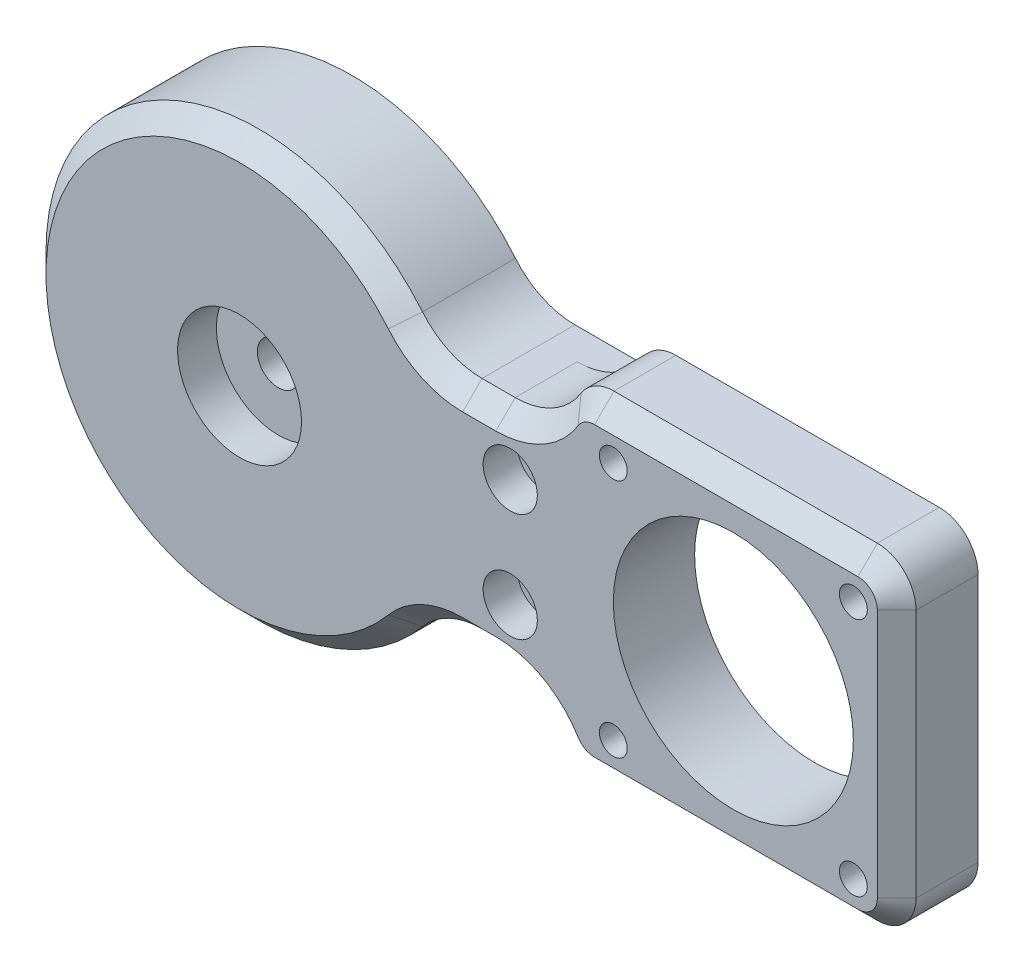
SolidWorks part; units mm, degrees
material "ABS"
ref_plane "Front Plane" through (0, 0, 0) normal (0, 0, 1) x (1, 0, 0)
ref_plane "Top Plane" through (0, 0, 0) normal (0, 1, 0) x (1, 0, 0)
ref_plane "Right Plane" through (0, 0, 0) normal (1, 0, 0) x (0, 0, -1)
sketch "Sketch1" plane through (0, 0, 0) normal (0, 0, 1) x (1, 0, 0)
  line L0 (42.6696, 14) -> (42.6696, 21.1)
  line L1 (23.6696, -14) -> (42.6696, -14)
  line L3 (23.6696, 14) -> (42.6696, 14)
  line L7 (42.6696, -21.1) -> (84.8696, -21.1)
  line L8 (42.6696, -21.1) -> (42.6696, -14)
  line L9 (42.6696, 21.1) -> (84.8696, 21.1)
  line L10 (84.8696, -21.1) -> (84.8696, 21.1)
  line L11 (42.6696, -21.1) -> (84.8696, 21.1) construction
  line L12 (42.6696, 21.1) -> (84.8696, -21.1) construction
  line L13 (48.2696, -15.5) -> (79.2696, -15.5) construction
  line L14 (48.2696, -15.5) -> (48.2696, 15.5) construction
  line L15 (48.2696, 15.5) -> (79.2696, 15.5) construction
  line L16 (79.2696, -15.5) -> (79.2696, 15.5) construction
  line L17 (48.2696, -15.5) -> (79.2696, 15.5) construction
  line L18 (48.2696, 15.5) -> (79.2696, -15.5) construction
  arc A0 (23.6696, 14) -> (23.6696, -14) centre (0, 0) ccw
  circle A2 centre (63.7696, 0) radius 15.5
  circle A3 centre (48.2696, 15.5) radius 1.5
  circle A4 centre (79.2696, 15.5) radius 1.5
  circle A5 centre (79.2696, -15.5) radius 1.5
  circle A6 centre (48.2696, -15.5) radius 1.5
  circle A7 centre (0, 0) radius 2.7
  point P3 (27.5, 0)
  point P8 (63.7696, 0)
  point P18 (63.7696, 0)
  dimension "D7" = 31
  dimension "D8" = 27.5
  dimension "D3" = 5.4
  dimension "D1" = 28
  dimension "D2" = 42.2
  dimension "D4" = 19
  dimension "D5" = 42.2
  dimension "D6" = 31
extrude "Boss-Extrude1" add sketch "Sketch1" along normal blind 14.5
ref_plane "Plane1" through (0, 0, 14.5) normal (0, 0, 1) x (1, 0, 0)
sketch "Sketch2" plane through (0, 0, 0) normal (0, 0, -1) x (-1, 0, 0)
  line L1 (-84.8696, -21.1) -> (-42.6696, -21.1)
  line L2 (-84.8696, -21.1) -> (-84.8696, 21.1)
  line L3 (-84.8696, 21.1) -> (-42.6696, 21.1)
  line L4 (-42.6696, -21.1) -> (-42.6696, 21.1)
  line L5 (-84.8696, -21.1) -> (-42.6696, 21.1) construction
  line L6 (-84.8696, 21.1) -> (-42.6696, -21.1) construction
  circle A0 centre (-63.7696, 0) radius 15.5 construction
  point P0 (-63.7696, 0)
extrude "Cut-Extrude1" cut sketch "Sketch2" against normal blind 4
sketch "Sketch3" plane through (0, 0, 14.5) normal (0, 0, 1) x (1, 0, 0)
  circle A0 centre (0, 0) radius 8
  dimension "D1" = 16
extrude "Cut-Extrude2" cut sketch "Sketch3" against normal blind 5
fillet "Fillet2" radius 10 4 edges at (42.6696, -14, 9.25) (42.6696, 14, 9.25) (23.6696, -14, 7.25) (23.6696, 14, 7.25)
sketch "Sketch5" plane through (0, 0, 14.5) normal (0, 0, 1) x (1, 0, 0)
  point P0 (79.2696, -15.5)
  point P3 (79.2696, 15.5)
  point P6 (48.2696, 15.5)
  point P9 (48.2696, -15.5)
hole_wizard "Taladro de margen para M31" positions "Sketch5" profile "Sketch6" hole size "M3" standard "Ansi Metric" end condition through all
sketch "Sketch6" plane through (79.2696, -15.5, 14.5) normal (1, 0, 0) x (0, -1, 0)
  line L0 (0, 0) -> (0, 14.5)
  line L1 (0, 14.5) -> (1.8, 14.5)
  line L2 (1.8, 14.5) -> (1.8, 0)
  line L5 (1.8, 0) -> (0, 0)
  line L11 (0, -6.35) -> (0, 107.95) construction
  dimension "Diámetro de taladro hasta el siguiente" = 3.6
  dimension "Profundidad de taladro hasta el siguiente" = 14.5
sketch "Sketch7" plane through (0, 0, 14.5) normal (0, 0, 1) x (1, 0, 0)
  line L0 (30.9567, 14) -> (30.9567, -14) construction
  line L1 (33.0993, 14) -> (28.8141, 14) construction
  line L2 (28.8141, -14) -> (33.0993, -14) construction
  line L3 (-969.0433, 0) -> (49030.9567, 0) construction
  line L4 (34.9567, -14) -> (34.9567, 14) construction
  circle A0 centre (34.9567, 7) radius 1.5
  circle A1 centre (34.9567, -7) radius 1.5
  point P11 (30.9567, 0)
  dimension "D2" = 3
  dimension "D1" = 7
  dimension "D3" = 7
  dimension "D4" = 4
extrude "Cut-Extrude3" cut sketch "Sketch7" against normal through all
sketch "Sketch8" plane through (0, 0, 14.5) normal (0, 0, 1) x (1, 0, 0)
  point P0 (34.9567, 7)
  point P3 (34.9567, -7)
hole_wizard "Refrentado para tornillo con cabeza troncocónica de M31" positions "Sketch8" profile "Sketch9" counterbore size "M3" standard "Ansi Metric" end condition through all
sketch "Sketch9" plane through (34.9567, 7, 14.5) normal (1, 0, 0) x (0, -1, 0)
  line L0 (0, 0) -> (0, 14.5)
  line L1 (0, 14.5) -> (1.8, 14.5)
  line L3 (1.8, 14.5) -> (1.8, 4.4)
  line L4 (1.8, 4.4) -> (3.5, 4.4)
  line L5 (3.5, 4.4) -> (3.5, 0)
  line L7 (3.5, 0) -> (0, 0)
  line L11 (0, -6.35) -> (0, 107.95) construction
  dimension "Diámetro de taladro hasta el siguiente" = 3.6
  dimension "Profundidad de taladro hasta el siguiente" = 14.5
  dimension "Diámetro de refrentado" = 7
  dimension "Profundidad de refrentado" = 4.4
fillet "Fillet3" radius 5 4 edges at (42.6696, -21.1, 9.25) (84.8696, -21.1, 9.25) (84.8696, 21.1, 9.25) (42.6696, 21.1, 9.25)
chamfer "Chamfer1" distance 2.5 angle 45 14 edges at (84.8696, 0, 14.5) (83.4051, 19.6355, 14.5) (83.4051, -19.6355, 14.5) (62.86, 21.1, 14.5) (62.86, -21.1, 14.5) (43.418, 20.4684, 14.5) (43.418, -20.4684, 14.5) (37.9642, 15.2631, 14.5) (37.9642, -15.2631, 14.5) (30.9567, 14, 14.5) (30.9567, -14, 14.5) (24.5714, 14.9446, 14.5) (24.5714, -14.9446, 14.5) (-27.5, 0, 14.5)
